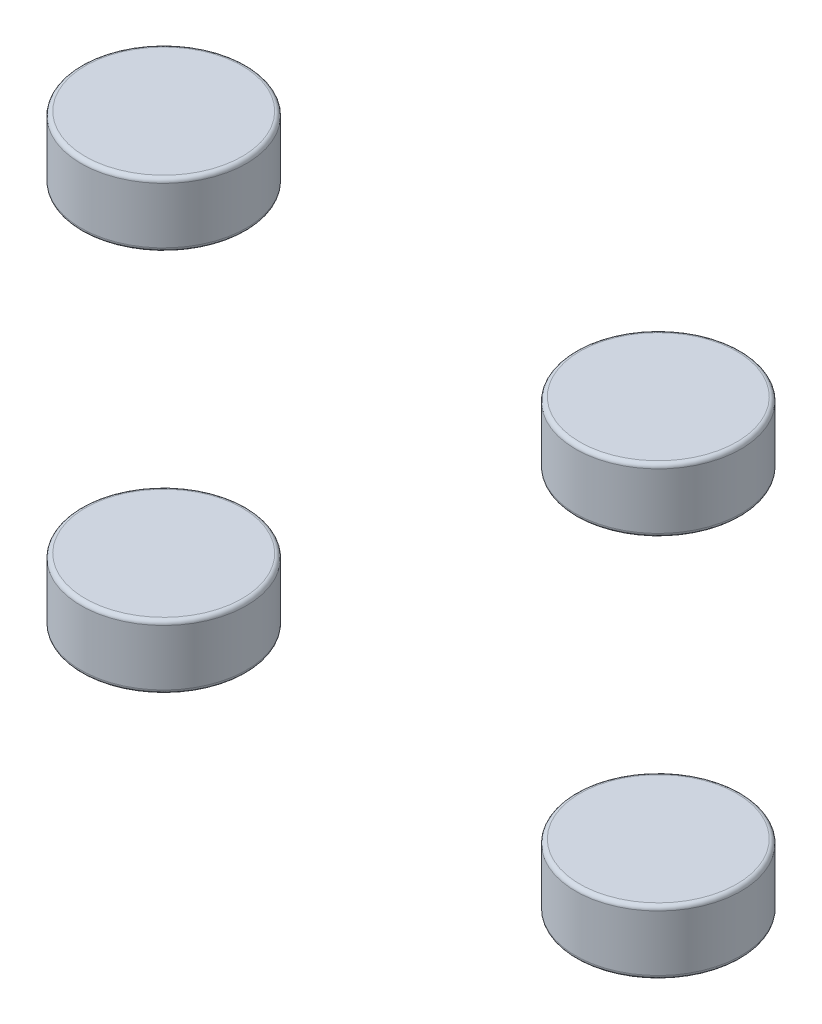
SolidWorks part; units mm, degrees
ref_plane "Front Plane" through (0, 0, 0) normal (0, 0, 1) x (1, 0, 0)
ref_plane "Top Plane" through (0, 0, 0) normal (0, 1, 0) x (1, 0, 0)
ref_plane "Right Plane" through (0, 0, 0) normal (1, 0, 0) x (0, 0, -1)
sketch3d "Left Suspension"
  line L0 (1180, -220, 108.03) -> (1122, -574, 138)
  line L1 (1122, -574, 138) -> (1020, -220, 136.03)
  line L2 (1020, -220, 136.03) -> (1180, -220, 108.03)
  line L3 (1030, -233, 255) -> (1170, -233, 242)
  line L4 (1170, -233, 242) -> (1150, -567.5, 313)
  line L5 (1150, -567.5, 313) -> (1030, -233, 255)
  line L6 (1165, -550.5, 318) -> (1165, -245, 393)
  line L7 (1165, -245, 393) -> (1165, -215, 393)
  line L8 (1165, -215, 393) -> (1165, -75, 333)
  line L9 (1165, -245, 393) -> (1155, -230, 333)
  line L10 (1155, -230, 333) -> (1175, -230, 333)
  line L11 (1175, -230, 333) -> (1165, -245, 393)
  line L12 (1165, -215, 393) -> (1155, -230, 333)
  line L13 (1165, -215, 393) -> (1175, -230, 333)
  line L14 (1244, -554, 222) -> (1251, -246, 222)
  line L15 (1130, -535, 233) -> (1244, -554, 222)
  line L16 (1130, -600, 235) -> (1130, -535, 233)
  line L34 (-420, -600, 235) -> (-420, -543.5, 233)
  line L35 (-420, -543.5, 233) -> (-412.5, -542, 156)
  line L36 (-490, -587, 155) -> (-491, -160, 151)
  line L37 (-412.5, -352, 446) -> (-446, -255, 425)
  line L38 (-380, -255, 425) -> (-412.5, -383, 405)
  line L39 (-446, -255, 425) -> (-412.5, -383, 405)
  line L40 (-380, -255, 425) -> (-446, -255, 425)
  line L41 (-412.5, -352, 446) -> (-380, -255, 425)
  line L42 (-412.5, -352, 446) -> (-412.5, -210.5, 587.5)
  line L43 (-412.5, -383, 405) -> (-412.5, -352, 446)
  line L44 (-412.5, -542, 156) -> (-412.5, -383, 405)
  line L45 (-578, -235, 280) -> (-416, -556, 332)
  line L46 (-270, -235, 280) -> (-578, -235, 280)
  line L47 (-416, -556, 332) -> (-270, -235, 280)
  line L48 (-427.5, -581, 127) -> (-236, -150, 142)
  line L49 (-536.5, -150, 117) -> (-427.5, -581, 127)
  line L50 (-236, -150, 142) -> (-536.5, -150, 117)
  point P0 (0, 0, 0)
  point P1 (1180, -220, 108.03)
  point P2 (1122, -574, 138)
  point P11 (1170, -233, 242)
sketch3d "3D Sketch 1"
  circle A0 centre (-420, -600, 235) radius 259
  circle A1 centre (1130, -600, 235) radius 259
  point P2 (-420, -341, 235)
  point P6 (1130, -341, 235)
  point P9 (1130, -600, 235)
  dimension "D1" = 518
  dimension "D2" = 518
extrude "Left Wheels" add sketch "3D Sketch 1" along direction (0, 1, 0) on the side against the normal blind 100.5 and the other way blind 100.5
fillet "Fillet1" radius 13 2 edges at (1130, -700.5, 494) (1130, -499.5, 494)
fillet "Fillet2" radius 13 2 edges at (-420, -700.5, 494) (-420, -499.5, 494)
sketch3d "Right sus"
  line L1 (1175, -230, 333) -> (1165, -245, 393) construction
  line L2 (1165, -215, 393) -> (1175, -230, 333) construction
  line L3 (1165, -245, 393) -> (1155, -230, 333) construction
  line L4 (1165, -215, 393) -> (1155, -230, 333) construction
  line L5 (1165, -215, 393) -> (1165, -75, 333) construction
  line L7 (1165, -550.5, 318) -> (1165, -245, 393) construction
  line L8 (1244, -554, 222) -> (1251, -246, 222) construction
  line L10 (1130, -600, 235) -> (1130, -535, 233) construction
  line L12 (-446, -255, 425) -> (-412.5, -383, 405) construction
  line L13 (-380, -255, 425) -> (-446, -255, 425) construction
  line L14 (-412.5, -352, 446) -> (-380, -255, 425) construction
  line L15 (-412.5, -352, 446) -> (-412.5, -210.5, 587.5) construction
  line L17 (-490, -587, 155) -> (-491, -160, 151) construction
  line L18 (-420, -600, 235) -> (-420, -543.5, 233) construction
  line L20 (-412.5, -542, 156) -> (-412.5, -383, 405) construction
  line L21 (-380, -255, 425) -> (-412.5, -383, 405) construction
  line L23 (1170, -233, 242) -> (1150, -567.5, 313) construction
  line L24 (1150, -567.5, 313) -> (1030, -233, 255) construction
  line L26 (1122, -574, 138) -> (1020, -220, 136.03) construction
  line L27 (1020, -220, 136.03) -> (1180, -220, 108.03) construction
  line L29 (-236, -150, 142) -> (-536.5, -150, 117) construction
  line L30 (-536.5, -150, 117) -> (-427.5, -581, 127) construction
  line L32 (-416, -556, 332) -> (-270, -235, 280) construction
  line L33 (-270, -235, 280) -> (-578, -235, 280) construction
  line L68 (-270, 235, 280) -> (-578, 235, 280)
  line L69 (-416, 556, 332) -> (-270, 235, 280)
  line L70 (-578, 235, 280) -> (-416, 556, 332)
  line L71 (-536.5, 150, 117) -> (-427.5, 581, 127)
  line L72 (-236, 150, 142) -> (-536.5, 150, 117)
  line L73 (-427.5, 581, 127) -> (-236, 150, 142)
  line L74 (1020, 220, 136.03) -> (1180, 220, 108.03)
  line L75 (1122, 574, 138) -> (1020, 220, 136.03)
  line L76 (1180, 220, 108.03) -> (1122, 574, 138)
  line L77 (1150, 567.5, 313) -> (1030, 233, 255)
  line L78 (1170, 233, 242) -> (1150, 567.5, 313)
  line L79 (1030, 233, 255) -> (1170, 233, 242)
  line L80 (-380, 255, 425) -> (-412.5, 383, 405)
  line L81 (-412.5, 542, 156) -> (-412.5, 383, 405)
  line L82 (-420, 543.5, 233) -> (-412.5, 542, 156)
  line L83 (-420, 600, 235) -> (-420, 543.5, 233)
  line L84 (-490, 587, 155) -> (-491, 160, 151)
  line L85 (-412.5, 383, 405) -> (-412.5, 352, 446)
  line L86 (-412.5, 352, 446) -> (-412.5, 210.5, 587.5)
  line L87 (-412.5, 352, 446) -> (-380, 255, 425)
  line L88 (-380, 255, 425) -> (-446, 255, 425)
  line L89 (-446, 255, 425) -> (-412.5, 383, 405)
  line L90 (-412.5, 352, 446) -> (-446, 255, 425)
  line L91 (1130, 600, 235) -> (1130, 535, 233)
  line L92 (1130, 535, 233) -> (1244, 554, 222)
  line L93 (1244, 554, 222) -> (1251, 246, 222)
  line L94 (1165, 550.5, 318) -> (1165, 245, 393)
  line L95 (1165, 245, 393) -> (1165, 215, 393)
  line L96 (1165, 215, 393) -> (1165, 75, 333)
  line L97 (1165, 215, 393) -> (1155, 230, 333)
  line L98 (1165, 245, 393) -> (1155, 230, 333)
  line L99 (1165, 215, 393) -> (1175, 230, 333)
  line L100 (1175, 230, 333) -> (1165, 245, 393)
  line L101 (1155, 230, 333) -> (1175, 230, 333)
sketch3d "3DSketch3"
  circle A0 centre (1130, 600, 235) radius 259
  circle A1 centre (-420, 600, 235) radius 259
  point P2 (1130, 859, 235)
  point P6 (-420, 859, 235)
  dimension "D1" = 518
  dimension "D2" = 518
extrude "Right Wheels" add sketch "3DSketch3" along direction (0, 1, 0) on the side of the normal blind 100.5 and the other way blind 100.5 separate body
fillet "Fillet4" radius 13 2 edges at (-420, 499.5, 494) (-420, 700.5, 494)
fillet "Fillet3" radius 13 2 edges at (1130, 499.5, 494) (1130, 700.5, 494)
ref_plane "Plane1" through (-936, 0, 0) normal (1, 0, 0) x (0, 0, -1)
ref_plane "Ground" through (0, 0, 494) normal (0, 0, 1) x (1, 0, 0)
sketch3d "3DSketch4"
  line L0 (0, 0, 0) -> (-807.2705, 0, 0)
  line L1 (-807.2705, 0, 0) -> (-807.2705, 0, 348.5334)
ref_plane "Plane3" through (0, 0, 0) normal (0, 1, 0) x (1, 0, 0)
